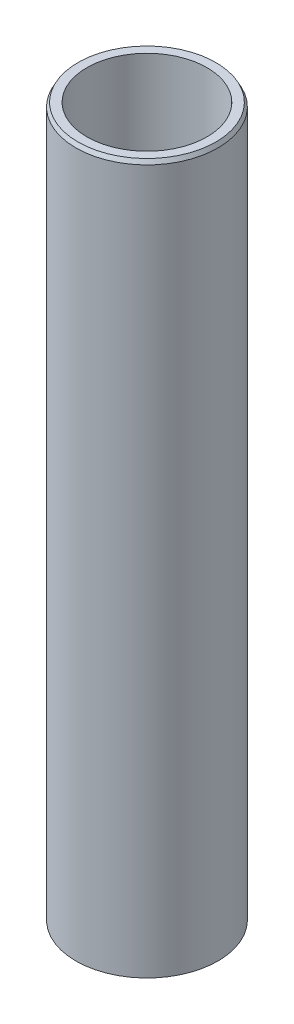
SolidWorks part; units mm, degrees
ref_plane "Front Plane" through (0, 0, 0) normal (0, 0, 1) x (1, 0, 0)
ref_plane "Top Plane" through (0, 0, 0) normal (0, 1, 0) x (1, 0, 0)
ref_plane "Right Plane" through (0, 0, 0) normal (1, 0, 0) x (0, 0, -1)
sketch "Sketch1" plane through (0, 0, 0) normal (0, 1, 0) x (1, 0, 0)
  circle A0 centre (0, 0) radius 60
  dimension "SHAFT_OD" = 120
extrude "Boss-Extrude1" add sketch "Sketch1" along normal blind 600
sketch "Sketch2" plane through (0, 0, 0) normal (0, 1, 0) x (1, 0, 0)
  circle A0 centre (0, 0) radius 50.7147
  dimension "BORE_D" = 101.4293
extrude "Cut-Extrude1" cut sketch "Sketch2" along normal through all
chamfer "Chamfer1" distance 3.4235 angle 27.74 2 edges at (0, 600, 60) (0, 0, 60) first distance on face at (0, 600, 60) first distance on face at (0, 0, 50.7147)
